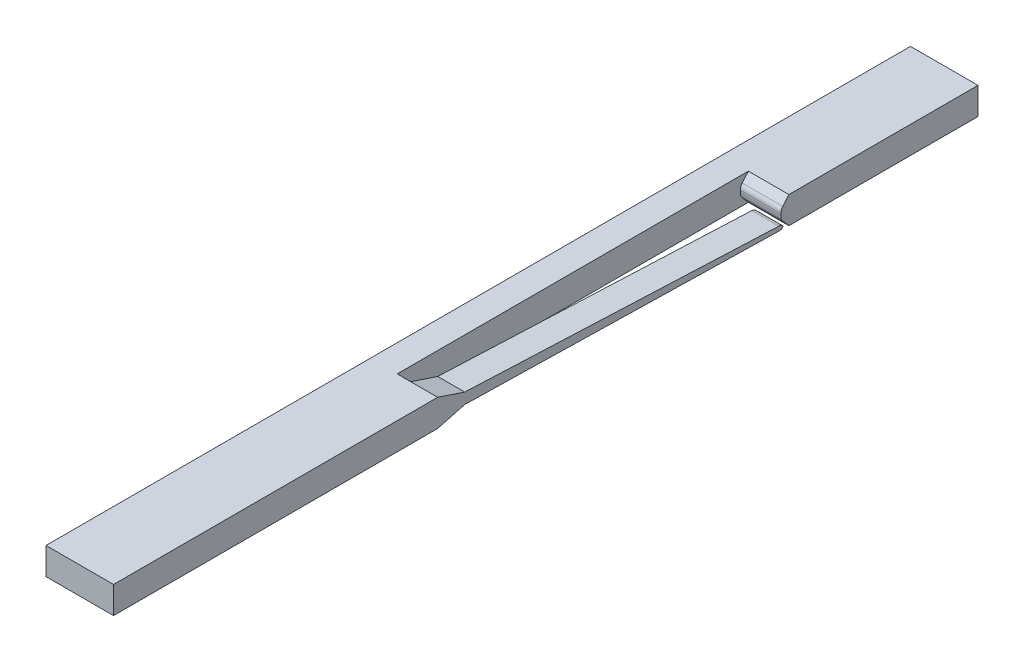
SolidWorks part; units mm, degrees
ref_plane "Front Plane" through (0, 0, 0) normal (0, 0, 1) x (1, 0, 0)
ref_plane "Top Plane" through (0, 0, 0) normal (0, 1, 0) x (1, 0, 0)
ref_plane "Right Plane" through (0, 0, 0) normal (1, 0, 0) x (0, 0, -1)
sketch "Sketch1" plane through (0, 0, 0) normal (1, 0, 0) x (0, 0, -1)
  line L1 (0, 0) -> (203.2, 0)
  line L2 (0, 0) -> (0, 6.35)
  line L3 (0, 6.35) -> (203.2, 6.35)
  line L4 (203.2, 0) -> (203.2, 6.35)
  dimension "D1" = 6.35
  dimension "D2" = 203.2
extrude "Boss-Extrude1" add sketch "Sketch1" against normal blind 6.35
sketch "Sketch2" plane through (0, 0, 0) normal (1, 0, 0) x (0, 0, -1)
  line L0 (0, 0) -> (203.2, 0) construction
  line L1 (0, 6.35) -> (76.2, 6.35)
  line L2 (0, 6.35) -> (0, 0)
  line L3 (0, 0) -> (76.2, 0)
  line L4 (76.2, 6.35) -> (76.2, 0)
  line L5 (203.2, 6.35) -> (0, 6.35) construction
  line L10 (203.2, 6.35) -> (158.75, 6.35)
  line L11 (203.2, 6.35) -> (203.2, 0)
  line L12 (203.2, 0) -> (158.75, 0)
  line L13 (158.75, 6.35) -> (158.75, 0)
  line L14 (203.2, 0) -> (203.2, 6.35) construction
  dimension "D1" = 76.2
  dimension "D2" = 44.45
extrude "Boss-Extrude2" add sketch "Sketch2" along normal blind 9.525
sketch "Sketch4" plane through (9.525, 0, 0) normal (1, 0, 0) x (0, 0, -1)
  line L0 (158.75, 6.35) -> (158.75, 0)
  line L1 (158.75, 6.35) -> (156.845, 4.1275)
  line L2 (156.845, 4.1275) -> (156.845, 2.2225)
  line L3 (156.845, 2.2225) -> (158.75, 0)
  line L4 (158.75, 3.175) -> (156.845, 3.175) construction
  line L5 (158.75, 6.35) -> (158.75, 0) construction
  line L6 (158.75, 6.35) -> (158.75, 0) construction
  dimension "D1" = 1.905
  dimension "D2" = 1.905
extrude "Boss-Extrude3" add sketch "Sketch4" against normal up to next
sketch "Sketch5" plane through (9.525, 0, 0) normal (1, 0, 0) x (0, 0, -1)
  line L0 (157.3213, 0.5556) -> (82.55, 2.97) construction
  line L1 (156.845, 2.2225) -> (156.845, 0) construction
  line L2 (157.3213, 0.5556) -> (76.2, 3.175)
  line L3 (76.2, 0) -> (76.2, 6.35) construction
  line L4 (82.55, 4.24) -> (82.55, 1.7)
  line L5 (82.55, 4.24) -> (76.2, 6.35)
  line L6 (82.55, 1.7) -> (76.2, 0)
  line L7 (76.2, 0) -> (76.2, 6.35)
  line L8 (156.3851, 1.0941) -> (82.55, 4.24)
  line L9 (82.55, 1.7) -> (156.3524, 0.0786)
  line L10 (76.2, 0) -> (158.75, 0) construction
  line L11 (156.845, 0) -> (157.7975, 1.1112) construction
  line L12 (156.845, 2.2225) -> (158.75, 0) construction
  ellipse E0 centre (156.3688, 0.5864) end of major axis (155.4163, 0.6171) minor radius 0.508
  point P11 (82.55, 2.97)
  line M9 (76.2, 0) -> (76.2, 6.35)
  dimension "D1" = 2.54
  dimension "D2" = 6.35
  dimension "D3" = 0.508
  dimension "D4" = 1.905
extrude "Boss-Extrude4" add sketch "Sketch5" against normal blind 6.35 contours L4 L5 L2 M9 | L6 L4 L2 M9 | L4 L2 | L2 L4 | E0 region at (9.525, 1.4831, -113.9414) region at (9.525, 2.4293, -113.9502) region at (9.525, 1.9078, -78.9214) region at (9.525, 4.2664, -78.9214)
fillet "Fillet1" radius 1.905 2 edges at (4.7625, 4.1275, -156.845) (4.7625, 2.2225, -156.845)
sketch "Sketch6" plane through (0, 6.35, 0) normal (0, 1, 0) x (1, 0, 0)
  line L0 (-6.35, 203.2) -> (9.525, 203.2) construction
  line L1 (-6.35, 203.2) -> (-6.35, 0) construction
  circle A0 centre (-6.096, 202.946) radius 0.127
  circle A1 centre (-5.334, 202.946) radius 0.127
  circle A2 centre (-4.572, 202.946) radius 0.127
  circle A3 centre (-3.81, 202.946) radius 0.127
  circle A4 centre (-3.048, 202.946) radius 0.127
  circle A5 centre (-2.286, 202.946) radius 0.127
  circle A6 centre (-1.524, 202.946) radius 0.127
  circle A7 centre (-0.762, 202.946) radius 0.127
  circle A8 centre (0, 202.946) radius 0.127
  circle A9 centre (0.762, 202.946) radius 0.127
  circle A10 centre (1.524, 202.946) radius 0.127
  circle A11 centre (2.286, 202.946) radius 0.127
  circle A12 centre (3.048, 202.946) radius 0.127
  circle A13 centre (3.81, 202.946) radius 0.127
  circle A14 centre (4.572, 202.946) radius 0.127
  circle A15 centre (5.334, 202.946) radius 0.127
  circle A16 centre (6.096, 202.946) radius 0.127
  circle A17 centre (6.858, 202.946) radius 0.127
  circle A18 centre (7.62, 202.946) radius 0.127
  circle A19 centre (8.382, 202.946) radius 0.127
  circle A20 centre (9.144, 202.946) radius 0.127
  circle A21 centre (-5.334, 202.184) radius 0.127
  circle A22 centre (-4.572, 202.184) radius 0.127
  circle A23 centre (-3.81, 202.184) radius 0.127
  circle A24 centre (-3.048, 202.184) radius 0.127
  circle A25 centre (-2.286, 202.184) radius 0.127
  circle A26 centre (-1.524, 202.184) radius 0.127
  circle A27 centre (-0.762, 202.184) radius 0.127
  circle A28 centre (0, 202.184) radius 0.127
  circle A29 centre (0.762, 202.184) radius 0.127
  circle A30 centre (1.524, 202.184) radius 0.127
  circle A31 centre (2.286, 202.184) radius 0.127
  circle A32 centre (3.048, 202.184) radius 0.127
  circle A33 centre (3.81, 202.184) radius 0.127
  circle A34 centre (4.572, 202.184) radius 0.127
  circle A35 centre (5.334, 202.184) radius 0.127
  circle A36 centre (6.096, 202.184) radius 0.127
  circle A37 centre (6.858, 202.184) radius 0.127
  circle A38 centre (7.62, 202.184) radius 0.127
  circle A39 centre (8.382, 202.184) radius 0.127
  circle A40 centre (9.144, 202.184) radius 0.127
  circle A41 centre (-5.334, 201.422) radius 0.127
  circle A42 centre (-4.572, 201.422) radius 0.127
  circle A43 centre (-3.81, 201.422) radius 0.127
  circle A44 centre (-3.048, 201.422) radius 0.127
  circle A45 centre (-2.286, 201.422) radius 0.127
  circle A46 centre (-1.524, 201.422) radius 0.127
  circle A47 centre (-0.762, 201.422) radius 0.127
  circle A48 centre (0, 201.422) radius 0.127
  circle A49 centre (0.762, 201.422) radius 0.127
  circle A50 centre (1.524, 201.422) radius 0.127
  circle A51 centre (2.286, 201.422) radius 0.127
  circle A52 centre (3.048, 201.422) radius 0.127
  circle A53 centre (3.81, 201.422) radius 0.127
  circle A54 centre (4.572, 201.422) radius 0.127
  circle A55 centre (5.334, 201.422) radius 0.127
  circle A56 centre (6.096, 201.422) radius 0.127
  circle A57 centre (6.858, 201.422) radius 0.127
  circle A58 centre (7.62, 201.422) radius 0.127
  circle A59 centre (8.382, 201.422) radius 0.127
  circle A60 centre (9.144, 201.422) radius 0.127
  circle A61 centre (-5.334, 200.66) radius 0.127
  circle A62 centre (-4.572, 200.66) radius 0.127
  circle A63 centre (-3.81, 200.66) radius 0.127
  circle A64 centre (-3.048, 200.66) radius 0.127
  circle A65 centre (-2.286, 200.66) radius 0.127
  circle A66 centre (-1.524, 200.66) radius 0.127
  circle A67 centre (-0.762, 200.66) radius 0.127
  circle A68 centre (0, 200.66) radius 0.127
  circle A69 centre (0.762, 200.66) radius 0.127
  circle A70 centre (1.524, 200.66) radius 0.127
  circle A71 centre (2.286, 200.66) radius 0.127
  circle A72 centre (3.048, 200.66) radius 0.127
  circle A73 centre (3.81, 200.66) radius 0.127
  circle A74 centre (4.572, 200.66) radius 0.127
  circle A75 centre (5.334, 200.66) radius 0.127
  circle A76 centre (6.096, 200.66) radius 0.127
  circle A77 centre (6.858, 200.66) radius 0.127
  circle A78 centre (7.62, 200.66) radius 0.127
  circle A79 centre (8.382, 200.66) radius 0.127
  circle A80 centre (9.144, 200.66) radius 0.127
  circle A81 centre (-5.334, 199.898) radius 0.127
  circle A82 centre (-4.572, 199.898) radius 0.127
  circle A83 centre (-3.81, 199.898) radius 0.127
  circle A84 centre (-3.048, 199.898) radius 0.127
  circle A85 centre (-2.286, 199.898) radius 0.127
  circle A86 centre (-1.524, 199.898) radius 0.127
  circle A87 centre (-0.762, 199.898) radius 0.127
  circle A88 centre (0, 199.898) radius 0.127
  circle A89 centre (0.762, 199.898) radius 0.127
  circle A90 centre (1.524, 199.898) radius 0.127
  circle A91 centre (2.286, 199.898) radius 0.127
  circle A92 centre (3.048, 199.898) radius 0.127
  circle A93 centre (3.81, 199.898) radius 0.127
  circle A94 centre (4.572, 199.898) radius 0.127
  circle A95 centre (5.334, 199.898) radius 0.127
  circle A96 centre (6.096, 199.898) radius 0.127
  circle A97 centre (6.858, 199.898) radius 0.127
  circle A98 centre (7.62, 199.898) radius 0.127
  circle A99 centre (8.382, 199.898) radius 0.127
  circle A100 centre (9.144, 199.898) radius 0.127
  circle A101 centre (-5.334, 199.136) radius 0.127
  circle A102 centre (-4.572, 199.136) radius 0.127
  circle A103 centre (-3.81, 199.136) radius 0.127
  circle A104 centre (-3.048, 199.136) radius 0.127
  circle A105 centre (-2.286, 199.136) radius 0.127
  circle A106 centre (-1.524, 199.136) radius 0.127
  circle A107 centre (-0.762, 199.136) radius 0.127
  circle A108 centre (0, 199.136) radius 0.127
  circle A109 centre (0.762, 199.136) radius 0.127
  circle A110 centre (1.524, 199.136) radius 0.127
  circle A111 centre (2.286, 199.136) radius 0.127
  circle A112 centre (3.048, 199.136) radius 0.127
  circle A113 centre (3.81, 199.136) radius 0.127
  circle A114 centre (4.572, 199.136) radius 0.127
  circle A115 centre (5.334, 199.136) radius 0.127
  circle A116 centre (6.096, 199.136) radius 0.127
  circle A117 centre (6.858, 199.136) radius 0.127
  circle A118 centre (7.62, 199.136) radius 0.127
  circle A119 centre (8.382, 199.136) radius 0.127
  circle A120 centre (9.144, 199.136) radius 0.127
  circle A121 centre (-5.334, 198.374) radius 0.127
  circle A122 centre (-4.572, 198.374) radius 0.127
  circle A123 centre (-3.81, 198.374) radius 0.127
  circle A124 centre (-3.048, 198.374) radius 0.127
  circle A125 centre (-2.286, 198.374) radius 0.127
  circle A126 centre (-1.524, 198.374) radius 0.127
  circle A127 centre (-0.762, 198.374) radius 0.127
  circle A128 centre (0, 198.374) radius 0.127
  circle A129 centre (0.762, 198.374) radius 0.127
  circle A130 centre (1.524, 198.374) radius 0.127
  circle A131 centre (2.286, 198.374) radius 0.127
  circle A132 centre (3.048, 198.374) radius 0.127
  circle A133 centre (3.81, 198.374) radius 0.127
  circle A134 centre (4.572, 198.374) radius 0.127
  circle A135 centre (5.334, 198.374) radius 0.127
  circle A136 centre (6.096, 198.374) radius 0.127
  circle A137 centre (6.858, 198.374) radius 0.127
  circle A138 centre (7.62, 198.374) radius 0.127
  circle A139 centre (8.382, 198.374) radius 0.127
  circle A140 centre (9.144, 198.374) radius 0.127
  circle A141 centre (-5.334, 197.612) radius 0.127
  circle A142 centre (-4.572, 197.612) radius 0.127
  circle A143 centre (-3.81, 197.612) radius 0.127
  circle A144 centre (-3.048, 197.612) radius 0.127
  circle A145 centre (-2.286, 197.612) radius 0.127
  circle A146 centre (-1.524, 197.612) radius 0.127
  circle A147 centre (-0.762, 197.612) radius 0.127
  circle A148 centre (0, 197.612) radius 0.127
  circle A149 centre (0.762, 197.612) radius 0.127
  circle A150 centre (1.524, 197.612) radius 0.127
  circle A151 centre (2.286, 197.612) radius 0.127
  circle A152 centre (3.048, 197.612) radius 0.127
  circle A153 centre (3.81, 197.612) radius 0.127
  circle A154 centre (4.572, 197.612) radius 0.127
  circle A155 centre (5.334, 197.612) radius 0.127
  circle A156 centre (6.096, 197.612) radius 0.127
  circle A157 centre (6.858, 197.612) radius 0.127
  circle A158 centre (7.62, 197.612) radius 0.127
  circle A159 centre (8.382, 197.612) radius 0.127
  circle A160 centre (9.144, 197.612) radius 0.127
  circle A161 centre (-5.334, 196.85) radius 0.127
  circle A162 centre (-4.572, 196.85) radius 0.127
  circle A163 centre (-3.81, 196.85) radius 0.127
  circle A164 centre (-3.048, 196.85) radius 0.127
  circle A165 centre (-2.286, 196.85) radius 0.127
  circle A166 centre (-1.524, 196.85) radius 0.127
  circle A167 centre (-0.762, 196.85) radius 0.127
  circle A168 centre (0, 196.85) radius 0.127
  circle A169 centre (0.762, 196.85) radius 0.127
  circle A170 centre (1.524, 196.85) radius 0.127
  circle A171 centre (2.286, 196.85) radius 0.127
  circle A172 centre (3.048, 196.85) radius 0.127
  circle A173 centre (3.81, 196.85) radius 0.127
  circle A174 centre (4.572, 196.85) radius 0.127
  circle A175 centre (5.334, 196.85) radius 0.127
  circle A176 centre (6.096, 196.85) radius 0.127
  circle A177 centre (6.858, 196.85) radius 0.127
  circle A178 centre (7.62, 196.85) radius 0.127
  circle A179 centre (8.382, 196.85) radius 0.127
  circle A180 centre (9.144, 196.85) radius 0.127
  circle A181 centre (-5.334, 196.088) radius 0.127
  circle A182 centre (-4.572, 196.088) radius 0.127
  circle A183 centre (-3.81, 196.088) radius 0.127
  circle A184 centre (-3.048, 196.088) radius 0.127
  circle A185 centre (-2.286, 196.088) radius 0.127
  circle A186 centre (-1.524, 196.088) radius 0.127
  circle A187 centre (-0.762, 196.088) radius 0.127
  circle A188 centre (0, 196.088) radius 0.127
  circle A189 centre (0.762, 196.088) radius 0.127
  circle A190 centre (1.524, 196.088) radius 0.127
  circle A191 centre (2.286, 196.088) radius 0.127
  circle A192 centre (3.048, 196.088) radius 0.127
  circle A193 centre (3.81, 196.088) radius 0.127
  circle A194 centre (4.572, 196.088) radius 0.127
  circle A195 centre (5.334, 196.088) radius 0.127
  circle A196 centre (6.096, 196.088) radius 0.127
  circle A197 centre (6.858, 196.088) radius 0.127
  circle A198 centre (7.62, 196.088) radius 0.127
  circle A199 centre (8.382, 196.088) radius 0.127
  circle A200 centre (9.144, 196.088) radius 0.127
  circle A201 centre (-5.334, 195.326) radius 0.127
  circle A202 centre (-4.572, 195.326) radius 0.127
  circle A203 centre (-3.81, 195.326) radius 0.127
  circle A204 centre (-3.048, 195.326) radius 0.127
  circle A205 centre (-2.286, 195.326) radius 0.127
  circle A206 centre (-1.524, 195.326) radius 0.127
  circle A207 centre (-0.762, 195.326) radius 0.127
  circle A208 centre (0, 195.326) radius 0.127
  circle A209 centre (0.762, 195.326) radius 0.127
  circle A210 centre (1.524, 195.326) radius 0.127
  circle A211 centre (2.286, 195.326) radius 0.127
  circle A212 centre (3.048, 195.326) radius 0.127
  circle A213 centre (3.81, 195.326) radius 0.127
  circle A214 centre (4.572, 195.326) radius 0.127
  circle A215 centre (5.334, 195.326) radius 0.127
  circle A216 centre (6.096, 195.326) radius 0.127
  circle A217 centre (6.858, 195.326) radius 0.127
  circle A218 centre (7.62, 195.326) radius 0.127
  circle A219 centre (8.382, 195.326) radius 0.127
  circle A220 centre (9.144, 195.326) radius 0.127
  circle A221 centre (-5.334, 194.564) radius 0.127
  circle A222 centre (-4.572, 194.564) radius 0.127
  circle A223 centre (-3.81, 194.564) radius 0.127
  circle A224 centre (-3.048, 194.564) radius 0.127
  circle A225 centre (-2.286, 194.564) radius 0.127
  circle A226 centre (-1.524, 194.564) radius 0.127
  circle A227 centre (-0.762, 194.564) radius 0.127
  circle A228 centre (0, 194.564) radius 0.127
  circle A229 centre (0.762, 194.564) radius 0.127
  circle A230 centre (1.524, 194.564) radius 0.127
  circle A231 centre (2.286, 194.564) radius 0.127
  circle A232 centre (3.048, 194.564) radius 0.127
  circle A233 centre (3.81, 194.564) radius 0.127
  circle A234 centre (4.572, 194.564) radius 0.127
  circle A235 centre (5.334, 194.564) radius 0.127
  circle A236 centre (6.096, 194.564) radius 0.127
  circle A237 centre (6.858, 194.564) radius 0.127
  circle A238 centre (7.62, 194.564) radius 0.127
  circle A239 centre (8.382, 194.564) radius 0.127
  circle A240 centre (9.144, 194.564) radius 0.127
  circle A241 centre (-5.334, 193.802) radius 0.127
  circle A242 centre (-4.572, 193.802) radius 0.127
  circle A243 centre (-3.81, 193.802) radius 0.127
  circle A244 centre (-3.048, 193.802) radius 0.127
  circle A245 centre (-2.286, 193.802) radius 0.127
  circle A246 centre (-1.524, 193.802) radius 0.127
  circle A247 centre (-0.762, 193.802) radius 0.127
  circle A248 centre (0, 193.802) radius 0.127
  circle A249 centre (0.762, 193.802) radius 0.127
  circle A250 centre (1.524, 193.802) radius 0.127
  circle A251 centre (2.286, 193.802) radius 0.127
  circle A252 centre (3.048, 193.802) radius 0.127
  circle A253 centre (3.81, 193.802) radius 0.127
  circle A254 centre (4.572, 193.802) radius 0.127
  circle A255 centre (5.334, 193.802) radius 0.127
  circle A256 centre (6.096, 193.802) radius 0.127
  circle A257 centre (6.858, 193.802) radius 0.127
  circle A258 centre (7.62, 193.802) radius 0.127
  circle A259 centre (8.382, 193.802) radius 0.127
  circle A260 centre (9.144, 193.802) radius 0.127
  circle A261 centre (-5.334, 193.04) radius 0.127
  circle A262 centre (-4.572, 193.04) radius 0.127
  circle A263 centre (-3.81, 193.04) radius 0.127
  circle A264 centre (-3.048, 193.04) radius 0.127
  circle A265 centre (-2.286, 193.04) radius 0.127
  circle A266 centre (-1.524, 193.04) radius 0.127
  circle A267 centre (-0.762, 193.04) radius 0.127
  circle A268 centre (0, 193.04) radius 0.127
  circle A269 centre (0.762, 193.04) radius 0.127
  circle A270 centre (1.524, 193.04) radius 0.127
  circle A271 centre (2.286, 193.04) radius 0.127
  circle A272 centre (3.048, 193.04) radius 0.127
  circle A273 centre (3.81, 193.04) radius 0.127
  circle A274 centre (4.572, 193.04) radius 0.127
  circle A275 centre (5.334, 193.04) radius 0.127
  circle A276 centre (6.096, 193.04) radius 0.127
  circle A277 centre (6.858, 193.04) radius 0.127
  circle A278 centre (7.62, 193.04) radius 0.127
  circle A279 centre (8.382, 193.04) radius 0.127
  circle A280 centre (9.144, 193.04) radius 0.127
  circle A281 centre (-5.334, 192.278) radius 0.127
  circle A282 centre (-4.572, 192.278) radius 0.127
  circle A283 centre (-3.81, 192.278) radius 0.127
  circle A284 centre (-3.048, 192.278) radius 0.127
  circle A285 centre (-2.286, 192.278) radius 0.127
  circle A286 centre (-1.524, 192.278) radius 0.127
  circle A287 centre (-0.762, 192.278) radius 0.127
  circle A288 centre (0, 192.278) radius 0.127
  circle A289 centre (0.762, 192.278) radius 0.127
  circle A290 centre (1.524, 192.278) radius 0.127
  circle A291 centre (2.286, 192.278) radius 0.127
  circle A292 centre (3.048, 192.278) radius 0.127
  circle A293 centre (3.81, 192.278) radius 0.127
  circle A294 centre (4.572, 192.278) radius 0.127
  circle A295 centre (5.334, 192.278) radius 0.127
  circle A296 centre (6.096, 192.278) radius 0.127
  circle A297 centre (6.858, 192.278) radius 0.127
  circle A298 centre (7.62, 192.278) radius 0.127
  circle A299 centre (8.382, 192.278) radius 0.127
  circle A300 centre (9.144, 192.278) radius 0.127
  circle A301 centre (-5.334, 191.516) radius 0.127
  circle A302 centre (-4.572, 191.516) radius 0.127
  circle A303 centre (-3.81, 191.516) radius 0.127
  circle A304 centre (-3.048, 191.516) radius 0.127
  circle A305 centre (-2.286, 191.516) radius 0.127
  circle A306 centre (-1.524, 191.516) radius 0.127
  circle A307 centre (-0.762, 191.516) radius 0.127
  circle A308 centre (0, 191.516) radius 0.127
  circle A309 centre (0.762, 191.516) radius 0.127
  circle A310 centre (1.524, 191.516) radius 0.127
  circle A311 centre (2.286, 191.516) radius 0.127
  circle A312 centre (3.048, 191.516) radius 0.127
  circle A313 centre (3.81, 191.516) radius 0.127
  circle A314 centre (4.572, 191.516) radius 0.127
  circle A315 centre (5.334, 191.516) radius 0.127
  circle A316 centre (6.096, 191.516) radius 0.127
  circle A317 centre (6.858, 191.516) radius 0.127
  circle A318 centre (7.62, 191.516) radius 0.127
  circle A319 centre (8.382, 191.516) radius 0.127
  circle A320 centre (9.144, 191.516) radius 0.127
  circle A321 centre (-5.334, 190.754) radius 0.127
  circle A322 centre (-4.572, 190.754) radius 0.127
  circle A323 centre (-3.81, 190.754) radius 0.127
  circle A324 centre (-3.048, 190.754) radius 0.127
  circle A325 centre (-2.286, 190.754) radius 0.127
  circle A326 centre (-1.524, 190.754) radius 0.127
  circle A327 centre (-0.762, 190.754) radius 0.127
  circle A328 centre (0, 190.754) radius 0.127
  circle A329 centre (0.762, 190.754) radius 0.127
  circle A330 centre (1.524, 190.754) radius 0.127
  circle A331 centre (2.286, 190.754) radius 0.127
  circle A332 centre (3.048, 190.754) radius 0.127
  circle A333 centre (3.81, 190.754) radius 0.127
  circle A334 centre (4.572, 190.754) radius 0.127
  circle A335 centre (5.334, 190.754) radius 0.127
  circle A336 centre (6.096, 190.754) radius 0.127
  circle A337 centre (6.858, 190.754) radius 0.127
  circle A338 centre (7.62, 190.754) radius 0.127
  circle A339 centre (8.382, 190.754) radius 0.127
  circle A340 centre (9.144, 190.754) radius 0.127
  circle A341 centre (-5.334, 189.992) radius 0.127
  circle A342 centre (-4.572, 189.992) radius 0.127
  circle A343 centre (-3.81, 189.992) radius 0.127
  circle A344 centre (-3.048, 189.992) radius 0.127
  circle A345 centre (-2.286, 189.992) radius 0.127
  circle A346 centre (-1.524, 189.992) radius 0.127
  circle A347 centre (-0.762, 189.992) radius 0.127
  circle A348 centre (0, 189.992) radius 0.127
  circle A349 centre (0.762, 189.992) radius 0.127
  circle A350 centre (1.524, 189.992) radius 0.127
  circle A351 centre (2.286, 189.992) radius 0.127
  circle A352 centre (3.048, 189.992) radius 0.127
  circle A353 centre (3.81, 189.992) radius 0.127
  circle A354 centre (4.572, 189.992) radius 0.127
  circle A355 centre (5.334, 189.992) radius 0.127
  circle A356 centre (6.096, 189.992) radius 0.127
  circle A357 centre (6.858, 189.992) radius 0.127
  circle A358 centre (7.62, 189.992) radius 0.127
  circle A359 centre (8.382, 189.992) radius 0.127
  circle A360 centre (9.144, 189.992) radius 0.127
  circle A361 centre (-5.334, 189.23) radius 0.127
  circle A362 centre (-4.572, 189.23) radius 0.127
  circle A363 centre (-3.81, 189.23) radius 0.127
  circle A364 centre (-3.048, 189.23) radius 0.127
  circle A365 centre (-2.286, 189.23) radius 0.127
  circle A366 centre (-1.524, 189.23) radius 0.127
  circle A367 centre (-0.762, 189.23) radius 0.127
  circle A368 centre (0, 189.23) radius 0.127
  circle A369 centre (0.762, 189.23) radius 0.127
  circle A370 centre (1.524, 189.23) radius 0.127
  circle A371 centre (2.286, 189.23) radius 0.127
  circle A372 centre (3.048, 189.23) radius 0.127
  circle A373 centre (3.81, 189.23) radius 0.127
  circle A374 centre (4.572, 189.23) radius 0.127
  circle A375 centre (5.334, 189.23) radius 0.127
  circle A376 centre (6.096, 189.23) radius 0.127
  circle A377 centre (6.858, 189.23) radius 0.127
  circle A378 centre (7.62, 189.23) radius 0.127
  circle A379 centre (8.382, 189.23) radius 0.127
  circle A380 centre (9.144, 189.23) radius 0.127
  circle A381 centre (-5.334, 188.468) radius 0.127
  circle A382 centre (-4.572, 188.468) radius 0.127
  circle A383 centre (-3.81, 188.468) radius 0.127
  circle A384 centre (-3.048, 188.468) radius 0.127
  circle A385 centre (-2.286, 188.468) radius 0.127
  circle A386 centre (-1.524, 188.468) radius 0.127
  circle A387 centre (-0.762, 188.468) radius 0.127
  circle A388 centre (0, 188.468) radius 0.127
  circle A389 centre (0.762, 188.468) radius 0.127
  circle A390 centre (1.524, 188.468) radius 0.127
  circle A391 centre (2.286, 188.468) radius 0.127
  circle A392 centre (3.048, 188.468) radius 0.127
  circle A393 centre (3.81, 188.468) radius 0.127
  circle A394 centre (4.572, 188.468) radius 0.127
  circle A395 centre (5.334, 188.468) radius 0.127
  circle A396 centre (6.096, 188.468) radius 0.127
  circle A397 centre (6.858, 188.468) radius 0.127
  circle A398 centre (7.62, 188.468) radius 0.127
  circle A399 centre (8.382, 188.468) radius 0.127
  circle A400 centre (9.144, 188.468) radius 0.127
  circle A401 centre (-5.334, 187.706) radius 0.127
  circle A402 centre (-4.572, 187.706) radius 0.127
  circle A403 centre (-3.81, 187.706) radius 0.127
  circle A404 centre (-3.048, 187.706) radius 0.127
  circle A405 centre (-2.286, 187.706) radius 0.127
  circle A406 centre (-1.524, 187.706) radius 0.127
  circle A407 centre (-0.762, 187.706) radius 0.127
  circle A408 centre (0, 187.706) radius 0.127
  circle A409 centre (0.762, 187.706) radius 0.127
  circle A410 centre (1.524, 187.706) radius 0.127
  circle A411 centre (2.286, 187.706) radius 0.127
  circle A412 centre (3.048, 187.706) radius 0.127
  circle A413 centre (3.81, 187.706) radius 0.127
  circle A414 centre (4.572, 187.706) radius 0.127
  circle A415 centre (5.334, 187.706) radius 0.127
  circle A416 centre (6.096, 187.706) radius 0.127
  circle A417 centre (6.858, 187.706) radius 0.127
  circle A418 centre (7.62, 187.706) radius 0.127
  circle A419 centre (8.382, 187.706) radius 0.127
  circle A420 centre (9.144, 187.706) radius 0.127
  circle A421 centre (-5.334, 186.944) radius 0.127
  circle A422 centre (-4.572, 186.944) radius 0.127
  circle A423 centre (-3.81, 186.944) radius 0.127
  circle A424 centre (-3.048, 186.944) radius 0.127
  circle A425 centre (-2.286, 186.944) radius 0.127
  circle A426 centre (-1.524, 186.944) radius 0.127
  circle A427 centre (-0.762, 186.944) radius 0.127
  circle A428 centre (0, 186.944) radius 0.127
  circle A429 centre (0.762, 186.944) radius 0.127
  circle A430 centre (1.524, 186.944) radius 0.127
  circle A431 centre (2.286, 186.944) radius 0.127
  circle A432 centre (3.048, 186.944) radius 0.127
  circle A433 centre (3.81, 186.944) radius 0.127
  circle A434 centre (4.572, 186.944) radius 0.127
  circle A435 centre (5.334, 186.944) radius 0.127
  circle A436 centre (6.096, 186.944) radius 0.127
  circle A437 centre (6.858, 186.944) radius 0.127
  circle A438 centre (7.62, 186.944) radius 0.127
  circle A439 centre (8.382, 186.944) radius 0.127
  circle A440 centre (9.144, 186.944) radius 0.127
  circle A441 centre (-5.334, 186.182) radius 0.127
  circle A442 centre (-4.572, 186.182) radius 0.127
  circle A443 centre (-3.81, 186.182) radius 0.127
  circle A444 centre (-3.048, 186.182) radius 0.127
  circle A445 centre (-2.286, 186.182) radius 0.127
  circle A446 centre (-1.524, 186.182) radius 0.127
  circle A447 centre (-0.762, 186.182) radius 0.127
  circle A448 centre (0, 186.182) radius 0.127
  circle A449 centre (0.762, 186.182) radius 0.127
  circle A450 centre (1.524, 186.182) radius 0.127
  circle A451 centre (2.286, 186.182) radius 0.127
  circle A452 centre (3.048, 186.182) radius 0.127
  circle A453 centre (3.81, 186.182) radius 0.127
  circle A454 centre (4.572, 186.182) radius 0.127
  circle A455 centre (5.334, 186.182) radius 0.127
  circle A456 centre (6.096, 186.182) radius 0.127
  circle A457 centre (6.858, 186.182) radius 0.127
  circle A458 centre (7.62, 186.182) radius 0.127
  circle A459 centre (8.382, 186.182) radius 0.127
  circle A460 centre (9.144, 186.182) radius 0.127
  circle A461 centre (-5.334, 185.42) radius 0.127
  circle A462 centre (-4.572, 185.42) radius 0.127
  circle A463 centre (-3.81, 185.42) radius 0.127
  circle A464 centre (-3.048, 185.42) radius 0.127
  circle A465 centre (-2.286, 185.42) radius 0.127
  circle A466 centre (-1.524, 185.42) radius 0.127
  circle A467 centre (-0.762, 185.42) radius 0.127
  circle A468 centre (0, 185.42) radius 0.127
  circle A469 centre (0.762, 185.42) radius 0.127
  circle A470 centre (1.524, 185.42) radius 0.127
  circle A471 centre (2.286, 185.42) radius 0.127
  circle A472 centre (3.048, 185.42) radius 0.127
  circle A473 centre (3.81, 185.42) radius 0.127
  circle A474 centre (4.572, 185.42) radius 0.127
  circle A475 centre (5.334, 185.42) radius 0.127
  circle A476 centre (6.096, 185.42) radius 0.127
  circle A477 centre (6.858, 185.42) radius 0.127
  circle A478 centre (7.62, 185.42) radius 0.127
  circle A479 centre (8.382, 185.42) radius 0.127
  circle A480 centre (9.144, 185.42) radius 0.127
  circle A481 centre (-5.334, 184.658) radius 0.127
  circle A482 centre (-4.572, 184.658) radius 0.127
  circle A483 centre (-3.81, 184.658) radius 0.127
  circle A484 centre (-3.048, 184.658) radius 0.127
  circle A485 centre (-2.286, 184.658) radius 0.127
  circle A486 centre (-1.524, 184.658) radius 0.127
  circle A487 centre (-0.762, 184.658) radius 0.127
  circle A488 centre (0, 184.658) radius 0.127
  circle A489 centre (0.762, 184.658) radius 0.127
  circle A490 centre (1.524, 184.658) radius 0.127
  circle A491 centre (2.286, 184.658) radius 0.127
  circle A492 centre (3.048, 184.658) radius 0.127
  circle A493 centre (3.81, 184.658) radius 0.127
  circle A494 centre (4.572, 184.658) radius 0.127
  circle A495 centre (5.334, 184.658) radius 0.127
  circle A496 centre (6.096, 184.658) radius 0.127
  circle A497 centre (6.858, 184.658) radius 0.127
  circle A498 centre (7.62, 184.658) radius 0.127
  circle A499 centre (8.382, 184.658) radius 0.127
  circle A500 centre (9.144, 184.658) radius 0.127
  circle A501 centre (-5.334, 183.896) radius 0.127
  circle A502 centre (-4.572, 183.896) radius 0.127
  circle A503 centre (-3.81, 183.896) radius 0.127
  circle A504 centre (-3.048, 183.896) radius 0.127
  circle A505 centre (-2.286, 183.896) radius 0.127
  circle A506 centre (-1.524, 183.896) radius 0.127
  circle A507 centre (-0.762, 183.896) radius 0.127
  circle A508 centre (0, 183.896) radius 0.127
  circle A509 centre (0.762, 183.896) radius 0.127
  circle A510 centre (1.524, 183.896) radius 0.127
  circle A511 centre (2.286, 183.896) radius 0.127
  circle A512 centre (3.048, 183.896) radius 0.127
  circle A513 centre (3.81, 183.896) radius 0.127
  circle A514 centre (4.572, 183.896) radius 0.127
  circle A515 centre (5.334, 183.896) radius 0.127
  circle A516 centre (6.096, 183.896) radius 0.127
  circle A517 centre (6.858, 183.896) radius 0.127
  circle A518 centre (7.62, 183.896) radius 0.127
  circle A519 centre (8.382, 183.896) radius 0.127
  circle A520 centre (9.144, 183.896) radius 0.127
  circle A521 centre (-5.334, 183.134) radius 0.127
  circle A522 centre (-4.572, 183.134) radius 0.127
  circle A523 centre (-3.81, 183.134) radius 0.127
  circle A524 centre (-3.048, 183.134) radius 0.127
  circle A525 centre (-2.286, 183.134) radius 0.127
  circle A526 centre (-1.524, 183.134) radius 0.127
  circle A527 centre (-0.762, 183.134) radius 0.127
  circle A528 centre (0, 183.134) radius 0.127
  circle A529 centre (0.762, 183.134) radius 0.127
  circle A530 centre (1.524, 183.134) radius 0.127
  circle A531 centre (2.286, 183.134) radius 0.127
  circle A532 centre (3.048, 183.134) radius 0.127
  circle A533 centre (3.81, 183.134) radius 0.127
  circle A534 centre (4.572, 183.134) radius 0.127
  circle A535 centre (5.334, 183.134) radius 0.127
  circle A536 centre (6.096, 183.134) radius 0.127
  circle A537 centre (6.858, 183.134) radius 0.127
  circle A538 centre (7.62, 183.134) radius 0.127
  circle A539 centre (8.382, 183.134) radius 0.127
  circle A540 centre (9.144, 183.134) radius 0.127
  circle A541 centre (-5.334, 182.372) radius 0.127
  circle A542 centre (-4.572, 182.372) radius 0.127
  circle A543 centre (-3.81, 182.372) radius 0.127
  circle A544 centre (-3.048, 182.372) radius 0.127
  circle A545 centre (-2.286, 182.372) radius 0.127
  circle A546 centre (-1.524, 182.372) radius 0.127
  circle A547 centre (-0.762, 182.372) radius 0.127
  circle A548 centre (0, 182.372) radius 0.127
  circle A549 centre (0.762, 182.372) radius 0.127
  circle A550 centre (1.524, 182.372) radius 0.127
  circle A551 centre (2.286, 182.372) radius 0.127
  circle A552 centre (3.048, 182.372) radius 0.127
  circle A553 centre (3.81, 182.372) radius 0.127
  circle A554 centre (4.572, 182.372) radius 0.127
  circle A555 centre (5.334, 182.372) radius 0.127
  circle A556 centre (6.096, 182.372) radius 0.127
  circle A557 centre (6.858, 182.372) radius 0.127
  circle A558 centre (7.62, 182.372) radius 0.127
  circle A559 centre (8.382, 182.372) radius 0.127
  circle A560 centre (9.144, 182.372) radius 0.127
  circle A561 centre (-5.334, 181.61) radius 0.127
  circle A562 centre (-4.572, 181.61) radius 0.127
  circle A563 centre (-3.81, 181.61) radius 0.127
  circle A564 centre (-3.048, 181.61) radius 0.127
  circle A565 centre (-2.286, 181.61) radius 0.127
  circle A566 centre (-1.524, 181.61) radius 0.127
  circle A567 centre (-0.762, 181.61) radius 0.127
  circle A568 centre (0, 181.61) radius 0.127
  circle A569 centre (0.762, 181.61) radius 0.127
  circle A570 centre (1.524, 181.61) radius 0.127
  circle A571 centre (2.286, 181.61) radius 0.127
  circle A572 centre (3.048, 181.61) radius 0.127
  circle A573 centre (3.81, 181.61) radius 0.127
  circle A574 centre (4.572, 181.61) radius 0.127
  circle A575 centre (5.334, 181.61) radius 0.127
  circle A576 centre (6.096, 181.61) radius 0.127
  circle A577 centre (6.858, 181.61) radius 0.127
  circle A578 centre (7.62, 181.61) radius 0.127
  circle A579 centre (8.382, 181.61) radius 0.127
  circle A580 centre (9.144, 181.61) radius 0.127
  circle A581 centre (-5.334, 180.848) radius 0.127
  circle A582 centre (-4.572, 180.848) radius 0.127
  circle A583 centre (-3.81, 180.848) radius 0.127
  circle A584 centre (-3.048, 180.848) radius 0.127
  circle A585 centre (-2.286, 180.848) radius 0.127
  circle A586 centre (-1.524, 180.848) radius 0.127
  circle A587 centre (-0.762, 180.848) radius 0.127
  circle A588 centre (0, 180.848) radius 0.127
  circle A589 centre (0.762, 180.848) radius 0.127
  circle A590 centre (1.524, 180.848) radius 0.127
  circle A591 centre (2.286, 180.848) radius 0.127
  circle A592 centre (3.048, 180.848) radius 0.127
  circle A593 centre (3.81, 180.848) radius 0.127
  circle A594 centre (4.572, 180.848) radius 0.127
  circle A595 centre (5.334, 180.848) radius 0.127
  circle A596 centre (6.096, 180.848) radius 0.127
  circle A597 centre (6.858, 180.848) radius 0.127
  circle A598 centre (7.62, 180.848) radius 0.127
  circle A599 centre (8.382, 180.848) radius 0.127
  circle A600 centre (9.144, 180.848) radius 0.127
  circle A601 centre (-5.334, 180.086) radius 0.127
  circle A602 centre (-4.572, 180.086) radius 0.127
  circle A603 centre (-3.81, 180.086) radius 0.127
  circle A604 centre (-3.048, 180.086) radius 0.127
  circle A605 centre (-2.286, 180.086) radius 0.127
  circle A606 centre (-1.524, 180.086) radius 0.127
  circle A607 centre (-0.762, 180.086) radius 0.127
  circle A608 centre (0, 180.086) radius 0.127
  circle A609 centre (0.762, 180.086) radius 0.127
  circle A610 centre (1.524, 180.086) radius 0.127
  circle A611 centre (2.286, 180.086) radius 0.127
  circle A612 centre (3.048, 180.086) radius 0.127
  circle A613 centre (3.81, 180.086) radius 0.127
  circle A614 centre (4.572, 180.086) radius 0.127
  circle A615 centre (5.334, 180.086) radius 0.127
  circle A616 centre (6.096, 180.086) radius 0.127
  circle A617 centre (6.858, 180.086) radius 0.127
  circle A618 centre (7.62, 180.086) radius 0.127
  circle A619 centre (8.382, 180.086) radius 0.127
  circle A620 centre (9.144, 180.086) radius 0.127
  circle A621 centre (-5.334, 179.324) radius 0.127
  circle A622 centre (-4.572, 179.324) radius 0.127
  circle A623 centre (-3.81, 179.324) radius 0.127
  circle A624 centre (-3.048, 179.324) radius 0.127
  circle A625 centre (-2.286, 179.324) radius 0.127
  circle A626 centre (-1.524, 179.324) radius 0.127
  circle A627 centre (-0.762, 179.324) radius 0.127
  circle A628 centre (0, 179.324) radius 0.127
  circle A629 centre (0.762, 179.324) radius 0.127
  circle A630 centre (1.524, 179.324) radius 0.127
  circle A631 centre (2.286, 179.324) radius 0.127
  circle A632 centre (3.048, 179.324) radius 0.127
  circle A633 centre (3.81, 179.324) radius 0.127
  circle A634 centre (4.572, 179.324) radius 0.127
  circle A635 centre (5.334, 179.324) radius 0.127
  circle A636 centre (6.096, 179.324) radius 0.127
  circle A637 centre (6.858, 179.324) radius 0.127
  circle A638 centre (7.62, 179.324) radius 0.127
  circle A639 centre (8.382, 179.324) radius 0.127
  circle A640 centre (9.144, 179.324) radius 0.127
  circle A641 centre (-5.334, 178.562) radius 0.127
  circle A642 centre (-4.572, 178.562) radius 0.127
  circle A643 centre (-3.81, 178.562) radius 0.127
  circle A644 centre (-3.048, 178.562) radius 0.127
  circle A645 centre (-2.286, 178.562) radius 0.127
  circle A646 centre (-1.524, 178.562) radius 0.127
  circle A647 centre (-0.762, 178.562) radius 0.127
  circle A648 centre (0, 178.562) radius 0.127
  circle A649 centre (0.762, 178.562) radius 0.127
  circle A650 centre (1.524, 178.562) radius 0.127
  circle A651 centre (2.286, 178.562) radius 0.127
  circle A652 centre (3.048, 178.562) radius 0.127
  circle A653 centre (3.81, 178.562) radius 0.127
  circle A654 centre (4.572, 178.562) radius 0.127
  circle A655 centre (5.334, 178.562) radius 0.127
  circle A656 centre (6.096, 178.562) radius 0.127
  circle A657 centre (6.858, 178.562) radius 0.127
  circle A658 centre (7.62, 178.562) radius 0.127
  circle A659 centre (8.382, 178.562) radius 0.127
  circle A660 centre (9.144, 178.562) radius 0.127
  circle A661 centre (-5.334, 177.8) radius 0.127
  circle A662 centre (-4.572, 177.8) radius 0.127
  circle A663 centre (-3.81, 177.8) radius 0.127
  circle A664 centre (-3.048, 177.8) radius 0.127
  circle A665 centre (-2.286, 177.8) radius 0.127
  circle A666 centre (-1.524, 177.8) radius 0.127
  circle A667 centre (-0.762, 177.8) radius 0.127
  circle A668 centre (0, 177.8) radius 0.127
  circle A669 centre (0.762, 177.8) radius 0.127
  circle A670 centre (1.524, 177.8) radius 0.127
  circle A671 centre (2.286, 177.8) radius 0.127
  circle A672 centre (3.048, 177.8) radius 0.127
  circle A673 centre (3.81, 177.8) radius 0.127
  circle A674 centre (4.572, 177.8) radius 0.127
  circle A675 centre (5.334, 177.8) radius 0.127
  circle A676 centre (6.096, 177.8) radius 0.127
  circle A677 centre (6.858, 177.8) radius 0.127
  circle A678 centre (7.62, 177.8) radius 0.127
  circle A679 centre (8.382, 177.8) radius 0.127
  circle A680 centre (9.144, 177.8) radius 0.127
  circle A681 centre (-5.334, 177.038) radius 0.127
  circle A682 centre (-4.572, 177.038) radius 0.127
  circle A683 centre (-3.81, 177.038) radius 0.127
  circle A684 centre (-3.048, 177.038) radius 0.127
  circle A685 centre (-2.286, 177.038) radius 0.127
  circle A686 centre (-1.524, 177.038) radius 0.127
  circle A687 centre (-0.762, 177.038) radius 0.127
  circle A688 centre (0, 177.038) radius 0.127
  circle A689 centre (0.762, 177.038) radius 0.127
  circle A690 centre (1.524, 177.038) radius 0.127
  circle A691 centre (2.286, 177.038) radius 0.127
  circle A692 centre (3.048, 177.038) radius 0.127
  circle A693 centre (3.81, 177.038) radius 0.127
  circle A694 centre (4.572, 177.038) radius 0.127
  circle A695 centre (5.334, 177.038) radius 0.127
  circle A696 centre (6.096, 177.038) radius 0.127
  circle A697 centre (6.858, 177.038) radius 0.127
  circle A698 centre (7.62, 177.038) radius 0.127
  circle A699 centre (8.382, 177.038) radius 0.127
  circle A700 centre (9.144, 177.038) radius 0.127
  circle A701 centre (-5.334, 176.276) radius 0.127
  circle A702 centre (-4.572, 176.276) radius 0.127
  circle A703 centre (-3.81, 176.276) radius 0.127
  circle A704 centre (-3.048, 176.276) radius 0.127
  circle A705 centre (-2.286, 176.276) radius 0.127
  circle A706 centre (-1.524, 176.276) radius 0.127
  circle A707 centre (-0.762, 176.276) radius 0.127
  circle A708 centre (0, 176.276) radius 0.127
  circle A709 centre (0.762, 176.276) radius 0.127
  circle A710 centre (1.524, 176.276) radius 0.127
  circle A711 centre (2.286, 176.276) radius 0.127
  circle A712 centre (3.048, 176.276) radius 0.127
  circle A713 centre (3.81, 176.276) radius 0.127
  circle A714 centre (4.572, 176.276) radius 0.127
  circle A715 centre (5.334, 176.276) radius 0.127
  circle A716 centre (6.096, 176.276) radius 0.127
  circle A717 centre (6.858, 176.276) radius 0.127
  circle A718 centre (7.62, 176.276) radius 0.127
  circle A719 centre (8.382, 176.276) radius 0.127
  circle A720 centre (9.144, 176.276) radius 0.127
  circle A721 centre (-5.334, 175.514) radius 0.127
  circle A722 centre (-4.572, 175.514) radius 0.127
  circle A723 centre (-3.81, 175.514) radius 0.127
  circle A724 centre (-3.048, 175.514) radius 0.127
  circle A725 centre (-2.286, 175.514) radius 0.127
  circle A726 centre (-1.524, 175.514) radius 0.127
  circle A727 centre (-0.762, 175.514) radius 0.127
  circle A728 centre (0, 175.514) radius 0.127
  circle A729 centre (0.762, 175.514) radius 0.127
  circle A730 centre (1.524, 175.514) radius 0.127
  circle A731 centre (2.286, 175.514) radius 0.127
  circle A732 centre (3.048, 175.514) radius 0.127
  circle A733 centre (3.81, 175.514) radius 0.127
  circle A734 centre (4.572, 175.514) radius 0.127
  circle A735 centre (5.334, 175.514) radius 0.127
  circle A736 centre (6.096, 175.514) radius 0.127
  circle A737 centre (6.858, 175.514) radius 0.127
  circle A738 centre (7.62, 175.514) radius 0.127
  circle A739 centre (8.382, 175.514) radius 0.127
  circle A740 centre (9.144, 175.514) radius 0.127
  circle A741 centre (-5.334, 174.752) radius 0.127
  circle A742 centre (-4.572, 174.752) radius 0.127
  circle A743 centre (-3.81, 174.752) radius 0.127
  circle A744 centre (-3.048, 174.752) radius 0.127
  circle A745 centre (-2.286, 174.752) radius 0.127
  circle A746 centre (-1.524, 174.752) radius 0.127
  circle A747 centre (-0.762, 174.752) radius 0.127
  circle A748 centre (0, 174.752) radius 0.127
  circle A749 centre (0.762, 174.752) radius 0.127
  circle A750 centre (1.524, 174.752) radius 0.127
  circle A751 centre (2.286, 174.752) radius 0.127
  circle A752 centre (3.048, 174.752) radius 0.127
  circle A753 centre (3.81, 174.752) radius 0.127
  circle A754 centre (4.572, 174.752) radius 0.127
  circle A755 centre (5.334, 174.752) radius 0.127
  circle A756 centre (6.096, 174.752) radius 0.127
  circle A757 centre (6.858, 174.752) radius 0.127
  circle A758 centre (7.62, 174.752) radius 0.127
  circle A759 centre (8.382, 174.752) radius 0.127
  circle A760 centre (9.144, 174.752) radius 0.127
  circle A761 centre (-5.334, 173.99) radius 0.127
  circle A762 centre (-4.572, 173.99) radius 0.127
  circle A763 centre (-3.81, 173.99) radius 0.127
  circle A764 centre (-3.048, 173.99) radius 0.127
  circle A765 centre (-2.286, 173.99) radius 0.127
  circle A766 centre (-1.524, 173.99) radius 0.127
  circle A767 centre (-0.762, 173.99) radius 0.127
  circle A768 centre (0, 173.99) radius 0.127
  circle A769 centre (0.762, 173.99) radius 0.127
  circle A770 centre (1.524, 173.99) radius 0.127
  circle A771 centre (2.286, 173.99) radius 0.127
  circle A772 centre (3.048, 173.99) radius 0.127
  circle A773 centre (3.81, 173.99) radius 0.127
  circle A774 centre (4.572, 173.99) radius 0.127
  circle A775 centre (5.334, 173.99) radius 0.127
  circle A776 centre (6.096, 173.99) radius 0.127
  circle A777 centre (6.858, 173.99) radius 0.127
  circle A778 centre (7.62, 173.99) radius 0.127
  circle A779 centre (8.382, 173.99) radius 0.127
  circle A780 centre (9.144, 173.99) radius 0.127
  circle A781 centre (-5.334, 173.228) radius 0.127
  circle A782 centre (-4.572, 173.228) radius 0.127
  circle A783 centre (-3.81, 173.228) radius 0.127
  circle A784 centre (-3.048, 173.228) radius 0.127
  circle A785 centre (-2.286, 173.228) radius 0.127
  circle A786 centre (-1.524, 173.228) radius 0.127
  circle A787 centre (-0.762, 173.228) radius 0.127
  circle A788 centre (0, 173.228) radius 0.127
  circle A789 centre (0.762, 173.228) radius 0.127
  circle A790 centre (1.524, 173.228) radius 0.127
  circle A791 centre (2.286, 173.228) radius 0.127
  circle A792 centre (3.048, 173.228) radius 0.127
  circle A793 centre (3.81, 173.228) radius 0.127
  circle A794 centre (4.572, 173.228) radius 0.127
  circle A795 centre (5.334, 173.228) radius 0.127
  circle A796 centre (6.096, 173.228) radius 0.127
  circle A797 centre (6.858, 173.228) radius 0.127
  circle A798 centre (7.62, 173.228) radius 0.127
  circle A799 centre (8.382, 173.228) radius 0.127
  circle A800 centre (9.144, 173.228) radius 0.127
  circle A801 centre (-5.334, 172.466) radius 0.127
  circle A802 centre (-4.572, 172.466) radius 0.127
  circle A803 centre (-3.81, 172.466) radius 0.127
  circle A804 centre (-3.048, 172.466) radius 0.127
  circle A805 centre (-2.286, 172.466) radius 0.127
  circle A806 centre (-1.524, 172.466) radius 0.127
  circle A807 centre (-0.762, 172.466) radius 0.127
  circle A808 centre (0, 172.466) radius 0.127
  circle A809 centre (0.762, 172.466) radius 0.127
  circle A810 centre (1.524, 172.466) radius 0.127
  circle A811 centre (2.286, 172.466) radius 0.127
  circle A812 centre (3.048, 172.466) radius 0.127
  circle A813 centre (3.81, 172.466) radius 0.127
  circle A814 centre (4.572, 172.466) radius 0.127
  circle A815 centre (5.334, 172.466) radius 0.127
  circle A816 centre (6.096, 172.466) radius 0.127
  circle A817 centre (6.858, 172.466) radius 0.127
  circle A818 centre (7.62, 172.466) radius 0.127
  circle A819 centre (8.382, 172.466) radius 0.127
  circle A820 centre (9.144, 172.466) radius 0.127
  circle A821 centre (-5.334, 171.704) radius 0.127
  circle A822 centre (-4.572, 171.704) radius 0.127
  circle A823 centre (-3.81, 171.704) radius 0.127
  circle A824 centre (-3.048, 171.704) radius 0.127
  circle A825 centre (-2.286, 171.704) radius 0.127
  circle A826 centre (-1.524, 171.704) radius 0.127
  circle A827 centre (-0.762, 171.704) radius 0.127
  circle A828 centre (0, 171.704) radius 0.127
  circle A829 centre (0.762, 171.704) radius 0.127
  circle A830 centre (1.524, 171.704) radius 0.127
  circle A831 centre (2.286, 171.704) radius 0.127
  circle A832 centre (3.048, 171.704) radius 0.127
  circle A833 centre (3.81, 171.704) radius 0.127
  circle A834 centre (4.572, 171.704) radius 0.127
  circle A835 centre (5.334, 171.704) radius 0.127
  circle A836 centre (6.096, 171.704) radius 0.127
  circle A837 centre (6.858, 171.704) radius 0.127
  circle A838 centre (7.62, 171.704) radius 0.127
  circle A839 centre (8.382, 171.704) radius 0.127
  circle A840 centre (9.144, 171.704) radius 0.127
  circle A841 centre (-5.334, 170.942) radius 0.127
  circle A842 centre (-4.572, 170.942) radius 0.127
  circle A843 centre (-3.81, 170.942) radius 0.127
  circle A844 centre (-3.048, 170.942) radius 0.127
  circle A845 centre (-2.286, 170.942) radius 0.127
  circle A846 centre (-1.524, 170.942) radius 0.127
  circle A847 centre (-0.762, 170.942) radius 0.127
  circle A848 centre (0, 170.942) radius 0.127
  circle A849 centre (0.762, 170.942) radius 0.127
  circle A850 centre (1.524, 170.942) radius 0.127
  circle A851 centre (2.286, 170.942) radius 0.127
  circle A852 centre (3.048, 170.942) radius 0.127
  circle A853 centre (3.81, 170.942) radius 0.127
  circle A854 centre (4.572, 170.942) radius 0.127
  circle A855 centre (5.334, 170.942) radius 0.127
  circle A856 centre (6.096, 170.942) radius 0.127
  circle A857 centre (6.858, 170.942) radius 0.127
  circle A858 centre (7.62, 170.942) radius 0.127
  circle A859 centre (8.382, 170.942) radius 0.127
  circle A860 centre (9.144, 170.942) radius 0.127
  circle A861 centre (-5.334, 170.18) radius 0.127
  circle A862 centre (-4.572, 170.18) radius 0.127
  circle A863 centre (-3.81, 170.18) radius 0.127
  circle A864 centre (-3.048, 170.18) radius 0.127
  circle A865 centre (-2.286, 170.18) radius 0.127
  circle A866 centre (-1.524, 170.18) radius 0.127
  circle A867 centre (-0.762, 170.18) radius 0.127
  circle A868 centre (0, 170.18) radius 0.127
  circle A869 centre (0.762, 170.18) radius 0.127
  circle A870 centre (1.524, 170.18) radius 0.127
  circle A871 centre (2.286, 170.18) radius 0.127
  circle A872 centre (3.048, 170.18) radius 0.127
  circle A873 centre (3.81, 170.18) radius 0.127
  circle A874 centre (4.572, 170.18) radius 0.127
  circle A875 centre (5.334, 170.18) radius 0.127
  circle A876 centre (6.096, 170.18) radius 0.127
  circle A877 centre (6.858, 170.18) radius 0.127
  circle A878 centre (7.62, 170.18) radius 0.127
  circle A879 centre (8.382, 170.18) radius 0.127
  circle A880 centre (9.144, 170.18) radius 0.127
  circle A881 centre (-5.334, 169.418) radius 0.127
  circle A882 centre (-4.572, 169.418) radius 0.127
  circle A883 centre (-3.81, 169.418) radius 0.127
  circle A884 centre (-3.048, 169.418) radius 0.127
  circle A885 centre (-2.286, 169.418) radius 0.127
  circle A886 centre (-1.524, 169.418) radius 0.127
  circle A887 centre (-0.762, 169.418) radius 0.127
  circle A888 centre (0, 169.418) radius 0.127
  circle A889 centre (0.762, 169.418) radius 0.127
  circle A890 centre (1.524, 169.418) radius 0.127
  circle A891 centre (2.286, 169.418) radius 0.127
  circle A892 centre (3.048, 169.418) radius 0.127
  circle A893 centre (3.81, 169.418) radius 0.127
  circle A894 centre (4.572, 169.418) radius 0.127
  circle A895 centre (5.334, 169.418) radius 0.127
  circle A896 centre (6.096, 169.418) radius 0.127
  circle A897 centre (6.858, 169.418) radius 0.127
  circle A898 centre (7.62, 169.418) radius 0.127
  circle A899 centre (8.382, 169.418) radius 0.127
  circle A900 centre (9.144, 169.418) radius 0.127
  circle A901 centre (-5.334, 168.656) radius 0.127
  circle A902 centre (-4.572, 168.656) radius 0.127
  circle A903 centre (-3.81, 168.656) radius 0.127
  circle A904 centre (-3.048, 168.656) radius 0.127
  circle A905 centre (-2.286, 168.656) radius 0.127
  circle A906 centre (-1.524, 168.656) radius 0.127
  circle A907 centre (-0.762, 168.656) radius 0.127
  circle A908 centre (0, 168.656) radius 0.127
  circle A909 centre (0.762, 168.656) radius 0.127
  circle A910 centre (1.524, 168.656) radius 0.127
  circle A911 centre (2.286, 168.656) radius 0.127
  circle A912 centre (3.048, 168.656) radius 0.127
  circle A913 centre (3.81, 168.656) radius 0.127
  circle A914 centre (4.572, 168.656) radius 0.127
  circle A915 centre (5.334, 168.656) radius 0.127
  circle A916 centre (6.096, 168.656) radius 0.127
  circle A917 centre (6.858, 168.656) radius 0.127
  circle A918 centre (7.62, 168.656) radius 0.127
  circle A919 centre (8.382, 168.656) radius 0.127
  circle A920 centre (9.144, 168.656) radius 0.127
  circle A921 centre (-5.334, 167.894) radius 0.127
  circle A922 centre (-4.572, 167.894) radius 0.127
  circle A923 centre (-3.81, 167.894) radius 0.127
  circle A924 centre (-3.048, 167.894) radius 0.127
  circle A925 centre (-2.286, 167.894) radius 0.127
  circle A926 centre (-1.524, 167.894) radius 0.127
  circle A927 centre (-0.762, 167.894) radius 0.127
  circle A928 centre (0, 167.894) radius 0.127
  circle A929 centre (0.762, 167.894) radius 0.127
  circle A930 centre (1.524, 167.894) radius 0.127
  circle A931 centre (2.286, 167.894) radius 0.127
  circle A932 centre (3.048, 167.894) radius 0.127
  circle A933 centre (3.81, 167.894) radius 0.127
  circle A934 centre (4.572, 167.894) radius 0.127
  circle A935 centre (5.334, 167.894) radius 0.127
  circle A936 centre (6.096, 167.894) radius 0.127
  circle A937 centre (6.858, 167.894) radius 0.127
  circle A938 centre (7.62, 167.894) radius 0.127
  circle A939 centre (8.382, 167.894) radius 0.127
  circle A940 centre (9.144, 167.894) radius 0.127
  circle A941 centre (-5.334, 167.132) radius 0.127
  circle A942 centre (-4.572, 167.132) radius 0.127
  circle A943 centre (-3.81, 167.132) radius 0.127
  circle A944 centre (-3.048, 167.132) radius 0.127
  circle A945 centre (-2.286, 167.132) radius 0.127
  circle A946 centre (-1.524, 167.132) radius 0.127
  circle A947 centre (-0.762, 167.132) radius 0.127
  circle A948 centre (0, 167.132) radius 0.127
  circle A949 centre (0.762, 167.132) radius 0.127
  circle A950 centre (1.524, 167.132) radius 0.127
  circle A951 centre (2.286, 167.132) radius 0.127
  circle A952 centre (3.048, 167.132) radius 0.127
  circle A953 centre (3.81, 167.132) radius 0.127
  circle A954 centre (4.572, 167.132) radius 0.127
  circle A955 centre (5.334, 167.132) radius 0.127
  circle A956 centre (6.096, 167.132) radius 0.127
  circle A957 centre (6.858, 167.132) radius 0.127
  circle A958 centre (7.62, 167.132) radius 0.127
  circle A959 centre (8.382, 167.132) radius 0.127
  circle A960 centre (9.144, 167.132) radius 0.127
  circle A961 centre (-5.334, 166.37) radius 0.127
  circle A962 centre (-4.572, 166.37) radius 0.127
  circle A963 centre (-3.81, 166.37) radius 0.127
  circle A964 centre (-3.048, 166.37) radius 0.127
  circle A965 centre (-2.286, 166.37) radius 0.127
  circle A966 centre (-1.524, 166.37) radius 0.127
  circle A967 centre (-0.762, 166.37) radius 0.127
  circle A968 centre (0, 166.37) radius 0.127
  circle A969 centre (0.762, 166.37) radius 0.127
  circle A970 centre (1.524, 166.37) radius 0.127
  circle A971 centre (2.286, 166.37) radius 0.127
  circle A972 centre (3.048, 166.37) radius 0.127
  circle A973 centre (3.81, 166.37) radius 0.127
  circle A974 centre (4.572, 166.37) radius 0.127
  circle A975 centre (5.334, 166.37) radius 0.127
  circle A976 centre (6.096, 166.37) radius 0.127
  circle A977 centre (6.858, 166.37) radius 0.127
  circle A978 centre (7.62, 166.37) radius 0.127
  circle A979 centre (8.382, 166.37) radius 0.127
  circle A980 centre (9.144, 166.37) radius 0.127
  circle A981 centre (-5.334, 165.608) radius 0.127
  circle A982 centre (-4.572, 165.608) radius 0.127
  circle A983 centre (-3.81, 165.608) radius 0.127
  circle A984 centre (-3.048, 165.608) radius 0.127
  circle A985 centre (-2.286, 165.608) radius 0.127
  circle A986 centre (-1.524, 165.608) radius 0.127
  circle A987 centre (-0.762, 165.608) radius 0.127
  circle A988 centre (0, 165.608) radius 0.127
  circle A989 centre (0.762, 165.608) radius 0.127
  circle A990 centre (1.524, 165.608) radius 0.127
  circle A991 centre (2.286, 165.608) radius 0.127
  circle A992 centre (3.048, 165.608) radius 0.127
  circle A993 centre (3.81, 165.608) radius 0.127
  circle A994 centre (4.572, 165.608) radius 0.127
  circle A995 centre (5.334, 165.608) radius 0.127
  circle A996 centre (6.096, 165.608) radius 0.127
  circle A997 centre (6.858, 165.608) radius 0.127
  circle A998 centre (7.62, 165.608) radius 0.127
  circle A999 centre (8.382, 165.608) radius 0.127
  circle A1000 centre (9.144, 165.608) radius 0.127
  circle A1001 centre (-6.096, 202.184) radius 0.127
  circle A1002 centre (-6.096, 201.422) radius 0.127
  circle A1003 centre (-6.096, 200.66) radius 0.127
  circle A1004 centre (-6.096, 199.898) radius 0.127
  circle A1005 centre (-6.096, 199.136) radius 0.127
  circle A1006 centre (-6.096, 198.374) radius 0.127
  circle A1007 centre (-6.096, 197.612) radius 0.127
  circle A1008 centre (-6.096, 196.85) radius 0.127
  circle A1009 centre (-6.096, 196.088) radius 0.127
  circle A1010 centre (-6.096, 195.326) radius 0.127
  circle A1011 centre (-6.096, 194.564) radius 0.127
  circle A1012 centre (-6.096, 193.802) radius 0.127
  circle A1013 centre (-6.096, 193.04) radius 0.127
  circle A1014 centre (-6.096, 192.278) radius 0.127
  circle A1015 centre (-6.096, 191.516) radius 0.127
  circle A1016 centre (-6.096, 190.754) radius 0.127
  circle A1017 centre (-6.096, 189.992) radius 0.127
  circle A1018 centre (-6.096, 189.23) radius 0.127
  circle A1019 centre (-6.096, 188.468) radius 0.127
  circle A1020 centre (-6.096, 187.706) radius 0.127
  circle A1021 centre (-6.096, 186.944) radius 0.127
  circle A1022 centre (-6.096, 186.182) radius 0.127
  circle A1023 centre (-6.096, 185.42) radius 0.127
  circle A1024 centre (-6.096, 184.658) radius 0.127
  circle A1025 centre (-6.096, 183.896) radius 0.127
  circle A1026 centre (-6.096, 183.134) radius 0.127
  circle A1027 centre (-6.096, 182.372) radius 0.127
  circle A1028 centre (-6.096, 181.61) radius 0.127
  circle A1029 centre (-6.096, 180.848) radius 0.127
  circle A1030 centre (-6.096, 180.086) radius 0.127
  circle A1031 centre (-6.096, 179.324) radius 0.127
  circle A1032 centre (-6.096, 178.562) radius 0.127
  circle A1033 centre (-6.096, 177.8) radius 0.127
  circle A1034 centre (-6.096, 177.038) radius 0.127
  circle A1035 centre (-6.096, 176.276) radius 0.127
  circle A1036 centre (-6.096, 175.514) radius 0.127
  circle A1037 centre (-6.096, 174.752) radius 0.127
  circle A1038 centre (-6.096, 173.99) radius 0.127
  circle A1039 centre (-6.096, 173.228) radius 0.127
  circle A1040 centre (-6.096, 172.466) radius 0.127
  circle A1041 centre (-6.096, 171.704) radius 0.127
  circle A1042 centre (-6.096, 170.942) radius 0.127
  circle A1043 centre (-6.096, 170.18) radius 0.127
  circle A1044 centre (-6.096, 169.418) radius 0.127
  circle A1045 centre (-6.096, 168.656) radius 0.127
  circle A1046 centre (-6.096, 167.894) radius 0.127
  circle A1047 centre (-6.096, 167.132) radius 0.127
  circle A1048 centre (-6.096, 166.37) radius 0.127
  circle A1049 centre (-6.096, 165.608) radius 0.127
  dimension "D1" = 0.254
  dimension "D2" = 0.254
  dimension "D3" = 0.254
  dimension "D4" = 21
  dimension "D5" = 50
extrude "Boss-Extrude5" [suppressed] add sketch "Sketch6" along normal blind 12.7
fillet "Fillet2" [suppressed] radius 1.905
